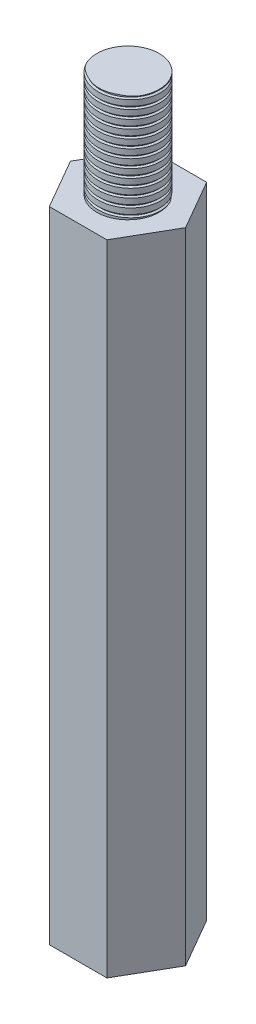
SolidWorks part; units mm, degrees
note: The reader was unsure of these and kept them because the rebuilt part matched: shared geometry of "草图1<3>".
ref_plane "前视基准面" through (0, 0, 0) normal (0, 0, 1) x (1, 0, 0)
ref_plane "上视基准面" through (0, 0, 0) normal (0, 1, 0) x (1, 0, 0)
ref_plane "右视基准面" through (0, 0, 0) normal (1, 0, 0) x (0, 0, -1)
sketch "草图1" plane through (0, 0, 0) normal (0, 1, 0) x (1, 0, 0)
  line L0 (0, 0) -> (0, 4.5761) construction
  line L1 (1.351, -2.34) -> (2.702, 0)
  line L2 (2.702, 0) -> (1.351, 2.34)
  line L3 (1.351, 2.34) -> (-1.351, 2.34)
  line L4 (-1.351, 2.34) -> (-2.702, 0)
  line L5 (-2.702, 0) -> (-1.351, -2.34)
  line L6 (-1.351, -2.34) -> (1.351, -2.34)
  line L7 (0, 4.5761) -> (0, -3.6794) construction
  circle A0 centre (0, 0) radius 2.34 construction
  circle A1 centre (0, 0) radius 1.46
  dimension "D1" = 4.68
  dimension "D2" = 2.92
extrude "凸台-拉伸1" add sketch "草图1" along normal blind 30 contours A1 | L5 L6 L1 L2 L3 L4 A1
extrude "切除-拉伸1" cut sketch "草图1<3>" along normal blind 5 contours A1
sketch "草图1<3>" plane through (0, 0, 0) normal (0, 1, 0) x (1, 0, 0) same geometry as "草图1"
sketch "草图2" plane through (0, 30, 0) normal (0, 1, 0) x (1, 0, 0)
  circle A0 centre (0, 0) radius 1.46
  dimension "D1" = 2.92
extrude "凸台-拉伸2" add sketch "草图2" along normal blind 5 separate body
ref_plane "基准面1" through (0, 0, 0) normal (0, 0, -1) x (-1, 0, 0)
sketch "草图4" plane through (0, 0, 0) normal (0, 0, -1) x (-1, 0, 0)
  line L0 (0, 0) -> (0, 28.5702) construction
  line L1 (-1.56, 30) -> (-1.56, 30.2)
  line L2 (-1.56, 30.2) -> (-1.36, 30.1333)
  line L3 (-1.36, 30.0667) -> (-1.56, 30)
  line L4 (-1.26, 30.1) -> (-2.0659, 30.1) construction
  line L5 (-2.0659, 30.1) -> (-0.8933, 30.1) construction
  line L7 (-1.46, 35) -> (-1.46, 30) construction
  line L8 (-1.36, 30.1333) -> (-1.36, 30.0667)
  line L9 (-1.46, 30) -> (1.46, 30) construction
  point P14 (0, 0)
  point P15 (0, 0)
  dimension "D1" = 0.1
  dimension "D2" = 0.1
  dimension "D3" = 0.1
  dimension "D4" = 0.3
  dimension "D5" = 0.2
  dimension "D6" = 0.1
  dimension "D7" = 0.0667
  dimension "D8" = 0.0667
ref_plane "基准面2" through (0, 30.1, 0) normal (0, 1, 0) x (1, 0, 0)
sketch "草图5" plane through (0, 30.1, 0) normal (0, 1, 0) x (1, 0, 0)
  circle A0 centre (0, 0) radius 1.46
  dimension "D1" = 2.92
curve "螺旋线/涡状线1" pitch 0.4 height 7.5 turns 18.75
sweep "切除-扫描1" cut profiles "草图4" path "螺旋线/涡状线1"
sketch "草图6" plane through (0, 0, 0) normal (0, -1, 0) x (1, 0, 0)
  circle A0 centre (0, 0) radius 1.46
curve "螺旋线/涡状线2" pitch 0.4 height 9.5 turns 23.75
sketch "草图7" plane through (0, 0, 0) normal (0, 0, -1) x (-1, 0, 0)
  line L0 (1.46, 0.2) -> (1.66, 0.1333)
  line L1 (1.66, 0.0667) -> (1.46, 0)
  line L2 (1.46, 0.2) -> (1.46, 0)
  line L3 (1.66, 0.1333) -> (1.66, 0.0667)
  line L8 (1.351, 0) -> (-1.351, 0) construction
  dimension "D1" = 0.2
  dimension "D3" = 1.46
  dimension "D4" = 0.2
sweep "切除-扫描2" cut profiles "草图7" path "螺旋线/涡状线2"
equation "\"chang\"= 20mm"
equation "\"r\"= 2.92mm"
equation "\"luowengao\"= 6.5mm"
equation "\"rr\"= 4.68mm"
equation "\"D1@草图1\"=\"rr\""
equation "\"D2@草图1\"=\"r\""
equation "\"D1@凸台-拉伸1\"=\"chang\""
equation "\"D1@切除-拉伸1\"=\"luowengao\"+5mm"
equation "\"D1@草图2\"=\"r\""
equation "\"D1@凸台-拉伸2\"=\"luowengao\""
